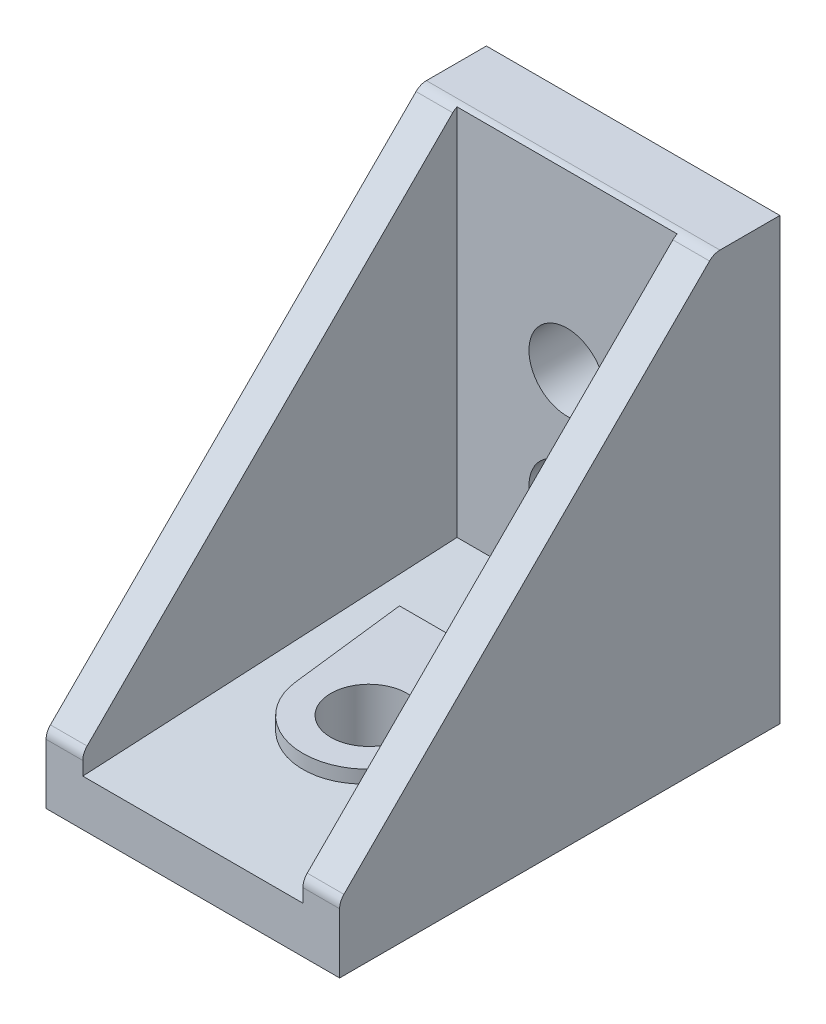
SolidWorks part; units mm, degrees
ref_plane "正面" through (0, 0, 0) normal (0, 0, 1) x (1, 0, 0)
ref_plane "平面" through (0, 0, 0) normal (0, 1, 0) x (1, 0, 0)
ref_plane "右側面" through (0, 0, 0) normal (1, 0, 0) x (0, 0, -1)
ref_plane "平面1" through (0, 0, 0) normal (1, 0, 0) x (0, 0, -1)
sketch "ｽｹｯﾁ1" plane through (0, 0, 0) normal (1, 0, 0) x (0, 0, -1)
  line L0 (-30, 4.0858) -> (-30, 0)
  line L1 (-30, 0) -> (0, 0)
  line L2 (0, 0) -> (0, 30)
  line L3 (0, 30) -> (-4.0858, 30)
  line L4 (-4.7929, 29.7071) -> (-29.7071, 4.7929)
  arc A0 (-4.0858, 30) -> (-4.7929, 29.7071) centre (-4.0858, 29) ccw
  arc A1 (-29.7071, 4.7929) -> (-30, 4.0858) centre (-29, 4.0858) ccw
extrude "ﾎﾞｽ - 押し出し1" add sketch "ｽｹｯﾁ1" against normal blind 10 and the other way blind 10
ref_plane "平面2" through (0, 0, 0) normal (1, 0, 0) x (0, 0, -1)
sketch "ｽｹｯﾁ2" plane through (0, 0, 0) normal (1, 0, 0) x (0, 0, -1)
  line L0 (-34.5, 34.5) -> (-34.5, 2.9278)
  line L1 (-34.5, 2.9278) -> (-4.5, 4.5)
  line L2 (-4.5, 4.5) -> (-4.5, 34.5)
  line L3 (-4.5, 34.5) -> (-34.5, 34.5)
extrude "ｶｯﾄ - 押し出し1" cut sketch "ｽｹｯﾁ2" against normal blind 7.5 and the other way blind 7.5
ref_plane "平面3" through (0, 4.5, 0) normal (0, 1, 0) x (1, 0, 0)
sketch "ｽｹｯﾁ3" plane through (0, 4.5, 0) normal (0, 1, 0) x (1, 0, 0)
  line L0 (-5.4209, -10.5) -> (-4.4687, -18.5299)
  line L1 (4.4687, -18.5299) -> (5.4209, -10.5)
  line L2 (5.4209, -10.5) -> (-5.4209, -10.5)
  arc A0 (-4.4687, -18.5299) -> (4.4687, -18.5299) centre (0, -18) ccw
extrude "ﾎﾞｽ - 押し出し2" add sketch "ｽｹｯﾁ3" against normal blind 2.25
ref_plane "平面4" through (0, 0, 0) normal (0, 0, 1) x (1, 0, 0)
sketch "ｽｹｯﾁ4" plane through (0, 0, 0) normal (0, 0, 1) x (1, 0, 0)
  circle A0 centre (0, 18) radius 2.6
extrude "ｶｯﾄ - 押し出し2" cut sketch "ｽｹｯﾁ4" along normal blind 4.5
ref_plane "平面5" through (0, 0, 0) normal (0, 0, 1) x (1, 0, 0)
sketch "ｽｹｯﾁ5" plane through (0, 0, 0) normal (0, 0, 1) x (1, 0, 0)
  circle A0 centre (0, 10) radius 2.6
extrude "ｶｯﾄ - 押し出し3" cut sketch "ｽｹｯﾁ5" along normal blind 4.5
ref_plane "平面6" through (0, 0, 0) normal (0, 1, 0) x (1, 0, 0)
sketch "ｽｹｯﾁ6" plane through (0, 0, 0) normal (0, 1, 0) x (1, 0, 0)
  circle A0 centre (0, -18) radius 2.6
extrude "ｶｯﾄ - 押し出し4" cut sketch "ｽｹｯﾁ6" along normal blind 4.5
ref_plane "平面7" through (0, 0, 0) normal (0, 1, 0) x (1, 0, 0)
sketch "ｽｹｯﾁ7" plane through (0, 0, 0) normal (0, 1, 0) x (1, 0, 0)
  line L0 (-10, -30) -> (10, -30)
  line L1 (10, -30) -> (10, 0)
  line L2 (10, 0) -> (-10, 0)
  line L3 (-10, 0) -> (-10, -30)
extrude "ﾎﾞｽ - 押し出し3" add sketch "ｽｹｯﾁ7" against normal blind 1
ref_plane "平面8" through (0, 0, 0) normal (0, 1, 0) x (1, 0, 0)
sketch "ｽｹｯﾁ8" plane through (0, 0, 0) normal (0, 1, 0) x (1, 0, 0)
  line L0 (-10, -30) -> (10, -30)
  line L1 (10, -30) -> (10, 0)
  line L2 (10, 0) -> (-10, 0)
  line L3 (-10, 0) -> (-10, -30)
  line L4 (-3, -24.3) -> (-3, -26.7)
  line L5 (-2.7, -27) -> (2.7, -27)
  line L6 (3, -26.7) -> (3, -24.3)
  line L7 (2.7, -24) -> (-2.7, -24)
  line L8 (-3, -5.3) -> (-3, -10.7)
  line L9 (-2.7, -11) -> (2.7, -11)
  line L10 (3, -10.7) -> (3, -5.3)
  line L11 (2.7, -5) -> (-2.7, -5)
  arc A0 (-3, -26.7) -> (-2.7, -27) centre (-2.7, -26.7) ccw
  arc A1 (2.7, -27) -> (3, -26.7) centre (2.7, -26.7) ccw
  arc A2 (3, -24.3) -> (2.7, -24) centre (2.7, -24.3) ccw
  arc A3 (-2.7, -24) -> (-3, -24.3) centre (-2.7, -24.3) ccw
  arc A4 (-3, -10.7) -> (-2.7, -11) centre (-2.7, -10.7) ccw
  arc A5 (2.7, -11) -> (3, -10.7) centre (2.7, -10.7) ccw
  arc A6 (3, -5.3) -> (2.7, -5) centre (2.7, -5.3) ccw
  arc A7 (-2.7, -5) -> (-3, -5.3) centre (-2.7, -5.3) ccw
extrude "ｶｯﾄ - 押し出し5" cut sketch "ｽｹｯﾁ8" against normal blind 1
